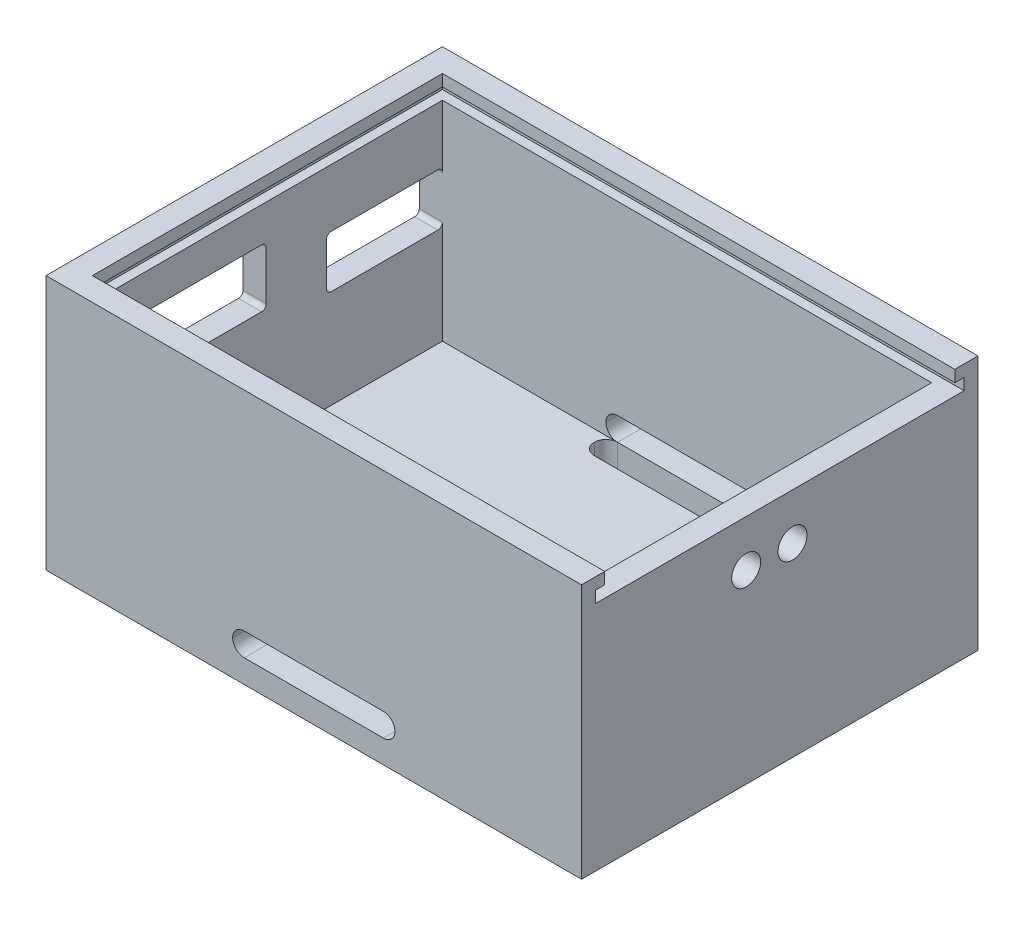
SolidWorks part; units mm, degrees
ref_plane "前视基准面" through (0, 0, 0) normal (0, 0, 1) x (1, 0, 0)
ref_plane "上视基准面" through (0, 0, 0) normal (0, 1, 0) x (1, 0, 0)
ref_plane "右视基准面" through (0, 0, 0) normal (1, 0, 0) x (0, 0, -1)
sketch "草图1" plane through (0, 0, 0) normal (0, 1, 0) x (1, 0, 0)
  line L1 (-23.1, 17.1) -> (23.1, 17.1)
  line L2 (-23.1, 17.1) -> (-23.1, -17.1)
  line L3 (-23.1, -17.1) -> (23.1, -17.1)
  line L4 (23.1, 17.1) -> (23.1, -17.1)
  line L5 (-23.1, 17.1) -> (23.1, -17.1) construction
  line L6 (-23.1, -17.1) -> (23.1, 17.1) construction
  point P0 (0, 0)
  dimension "D1" = 46.2
  dimension "D2" = 34.2
extrude "凸台-拉伸1" add sketch "草图1" along normal blind 22
shell "抽壳1" thickness 2 removed face at (0, 22, 0)
sketch "草图2" plane through (23.1, 0, 0) normal (1, 0, 0) x (0, 0, -1)
  line L0 (-17.1, 22) -> (17.1, 22) construction
  line L1 (-6, 22) -> (6, 22)
  line L2 (-6, 22) -> (-6, 15)
  line L3 (-6, 15) -> (6, 15)
  line L4 (6, 22) -> (6, 15)
  point P6 (0, 22)
  dimension "D1" = 7
  dimension "D2" = 12
extrude "切除-拉伸1" [suppressed] cut sketch "草图2" against normal up to next
sketch "草图3" plane through (-21.1, 0, 0) normal (1, 0, 0) x (0, 0, -1)
  line L0 (15.1, 2) -> (-15.1, 2) construction
  line L1 (-5, 15) -> (5, 15)
  line L2 (-5, 15) -> (-5, 11)
  line L3 (-5, 11) -> (5, 11)
  line L4 (5, 15) -> (5, 11)
  point P6 (0, 15)
  dimension "D1" = 9
  dimension "D2" = 10
  dimension "D3" = 4
extrude "切除-拉伸2" [suppressed] cut sketch "草图3" against normal up to next
fillet "圆角1" [suppressed] radius 1
fillet "圆角2" [suppressed] radius 2
sketch "草图4" plane through (23.1, 0, 0) normal (1, 0, 0) x (0, 0, -1)
  line L0 (-17.1, 22) -> (17.1, 22) construction
  line L1 (-15.1, 22) -> (15.1, 22)
  line L2 (-15.1, 22) -> (-15.1, 20)
  line L3 (-15.1, 20) -> (15.1, 20)
  line L4 (15.1, 22) -> (15.1, 20)
  line L5 (-15.1, 22) -> (-15.1, 2) construction
  line L6 (15.1, 22) -> (15.1, 2) construction
  dimension "D1" = 2
extrude "切除-拉伸3" cut sketch "草图4" against normal up to next
sketch "草图5" plane through (23.1, 0, 0) normal (1, 0, 0) x (0, 0, -1)
  line L0 (-17.1, 22) -> (-17.1, 0) construction
  line L1 (-15.9, 21) -> (15.9, 21)
  line L2 (-15.9, 21) -> (-15.9, 20)
  line L3 (-15.9, 20) -> (15.9, 20)
  line L4 (15.9, 21) -> (15.9, 20)
  line L5 (17.1, 22) -> (17.1, 0) construction
  line L6 (-17.1, 22) -> (-15.1, 22) construction
  dimension "D1" = 1.2
  dimension "D2" = 1.2
  dimension "D3" = 1
  dimension "D4" = 1
extrude "切除-拉伸4" cut sketch "草图5" against normal offset from surface (45 mm away) 0.8 up to face at (-21.1, 12, 0) offset beyond the face yes
sketch "草图6" plane through (-23.1, 0, 0) normal (-1, 0, 0) x (0, 0, 1)
  line L0 (-17.1, 22) -> (-17.1, 0) construction
  line L1 (17.1, 22) -> (17.1, 0) construction
  line L3 (15.9, 20) -> (15.9, 21) construction
  circle A0 centre (-11.1, 20.5) radius 0.8
  circle A1 centre (11.1, 20.5) radius 0.8
  point P10 (15.9, 20.5)
  dimension "D1" = 1.6
  dimension "D2" = 6
  dimension "D3" = 6
extrude "切除-拉伸5" [suppressed] cut sketch "草图6" against normal up to next
sketch "草图8" plane through (0, 0, 0) normal (0, -1, 0) x (1, 0, 0)
  line L0 (23.1, -17.1) -> (-23.1, -17.1) construction
  line L1 (-7, -13.1) -> (7, -13.1)
  line L2 (-7, -13.1) -> (-7, -15.1)
  line L3 (-7, -15.1) -> (7, -15.1)
  line L4 (7, -13.1) -> (7, -15.1)
  point P6 (0, -13.1)
  dimension "D1" = 14
  dimension "D2" = 2
  dimension "D3" = 2
extrude "切除-拉伸6" cut sketch "草图8" against normal up to next
sketch "草图9" plane through (0, 0, -17.1) normal (0, 0, -1) x (-1, 0, 0)
  line L0 (-23.1, 0) -> (23.1, 0) construction
  line L1 (-7, 4) -> (7, 4)
  line L2 (-7, 4) -> (-7, 2)
  line L3 (-7, 2) -> (7, 2)
  line L4 (7, 4) -> (7, 2)
  point P6 (0, 4)
  dimension "D1" = 14
  dimension "D2" = 2
  dimension "D3" = 2
extrude "切除-拉伸7" cut sketch "草图9" against normal up to next
fillet "圆角3" radius 1 4 edges at (-7, 4, -16.1) (-7, 2, -16.1) (7, 2, -16.1) (7, 4, -16.1)
fillet "圆角4" radius 1 4 edges at (-7, 1, -15.1) (-7, 1, -13.1) (7, 1, -15.1) (7, 1, -13.1)
mirror "镜向1" about plane through (0, 0, 0) normal (0, 0, 1) of "圆角4", "圆角3", "切除-拉伸6", "切除-拉伸7"
sketch "草图10" plane through (-23.1, 0, 0) normal (-1, 0, 0) x (0, 0, 1)
  line L0 (-15.1, 2) -> (-15.1, 3) construction
  line L1 (-15.1, 15) -> (-5.1, 15)
  line L2 (-15.1, 15) -> (-15.1, 10.5)
  line L3 (-15.1, 10.5) -> (-5.1, 10.5)
  line L4 (-5.1, 15) -> (-5.1, 10.5)
  line L5 (-15.1, 2) -> (15.1, 2) construction
  dimension "D1" = 10
  dimension "D2" = 8.5
  dimension "D3" = 4.5
extrude "切除-拉伸8" cut sketch "草图10" against normal up to next
fillet "圆角6" radius 0.4 4 edges at (-22.1, 15, -15.1) (-22.1, 15, -5.1) (-22.1, 10.5, -5.1) (-22.1, 10.5, -15.1)
sketch "草图11" plane through (-23.1, 0, 0) normal (-1, 0, 0) x (0, 0, 1)
  line L0 (-15.1, 2) -> (15.1, 2) construction
  line L1 (11.1, 12) -> (0.1, 12)
  line L2 (11.1, 12) -> (11.1, 17)
  line L3 (11.1, 17) -> (0.1, 17)
  line L4 (0.1, 12) -> (0.1, 17)
  line L6 (15.1, 20) -> (15.1, 2) construction
  dimension "D1" = 10
  dimension "D2" = 5
  dimension "D3" = 11
  dimension "D4" = 4
extrude "切除-拉伸9" cut sketch "草图11" against normal up to next
fillet "圆角7" radius 0.4 4 edges at (-22.1, 17, 0.1) (-22.1, 17, 11.1) (-22.1, 12, 11.1) (-22.1, 12, 0.1)
sketch "草图12" plane through (23.1, 0, 0) normal (1, 0, 0) x (0, 0, -1)
  line L0 (-2.9, 16) -> (1.1, 16) construction
  line L1 (15.1, 20) -> (15.1, 2) construction
  line L2 (-15.1, 2) -> (15.1, 2) construction
  circle A0 centre (-2.9, 16) radius 1.25
  circle A1 centre (1.1, 16) radius 1.25
  point P4 (-0.9, 16)
  dimension "D1" = 2.5
  dimension "D2" = 4
  dimension "D3" = 16
  dimension "D4" = 14
extrude "切除-拉伸10" cut sketch "草图12" against normal up to next
